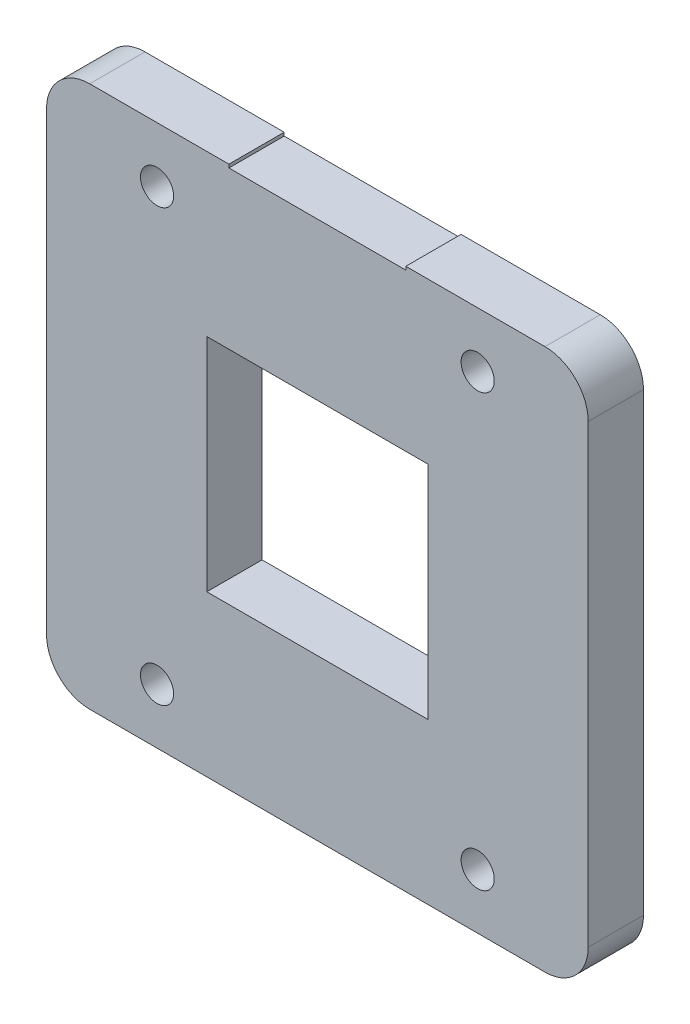
SolidWorks part; units mm, degrees
ref_plane "Front Plane" through (0, 0, 0) normal (0, 0, 1) x (1, 0, 0)
ref_plane "Top Plane" through (0, 0, 0) normal (0, 1, 0) x (1, 0, 0)
ref_plane "Right Plane" through (0, 0, 0) normal (1, 0, 0) x (0, 0, -1)
sketch "Sketch1" plane through (0, 0, 0) normal (0, 0, 1) x (1, 0, 0)
  line L0 (-20.59, 24.5) -> (20.59, 24.5)
  line L1 (-24.5, 20.59) -> (-24.5, -20.59)
  line L2 (-20.59, -24.5) -> (21.2574, -24.5)
  line L3 (24.5, 20.59) -> (24.5, -20.59)
  line L4 (20.59, -24.5) -> (21.2574, -24.5)
  arc A0 (-20.59, 24.5) -> (-24.5, 20.59) centre (-20.59, 20.59) ccw
  arc A1 (-24.5, -20.59) -> (-20.59, -24.5) centre (-20.59, -20.59) ccw
  arc A2 (20.59, 24.5) -> (24.5, 20.59) centre (20.59, 20.59) cw
  arc A3 (24.5, -20.59) -> (20.59, -24.5) centre (20.59, -20.59) cw
  point P2 (0, 24.5)
  point P17 (-24.5, 0)
  dimension "D1" = 3.91
  dimension "D2" = 41.18
  dimension "D3" = 41.18
extrude "Boss-Extrude1" add sketch "Sketch1" along normal blind 5 contours A3 L3 A2 L0 A0 L1 A1 L2 region at (0, 0, 0)
sketch "Sketch2" plane through (0, 0, 5) normal (0, 0, 1) x (1, 0, 0)
  line L6 (-10, -10) -> (10, -10)
  line L7 (-10, -10) -> (-10, 10)
  line L8 (-10, 10) -> (10, 10)
  line L9 (10, -10) -> (10, 10)
  line L10 (-10, -10) -> (10, 10) construction
  line L11 (-10, 10) -> (10, -10) construction
  point P0 (0, 0)
  dimension "D1" = 20
extrude "Cut-Extrude1" cut sketch "Sketch2" against normal blind 5 contours L6 L9 L8 L7 region at (0, 0, 5)
sketch "Sketch5" plane through (0, 0, 5) normal (0, 0, 1) x (1, 0, 0)
  line L2 (-24.5, 20.59) -> (-24.5, -20.59) construction
  line L5 (24.5, 20.59) -> (24.5, -20.59) construction
  line L6 (-20.59, 24.5) -> (20.59, 24.5) construction
  line L7 (-20.59, -24.5) -> (20.59, -24.5) construction
  circle A0 centre (-14.5, 19.5) radius 1.5
  circle A1 centre (14.5, 19.5) radius 1.5
  circle A2 centre (-14.5, -19.5) radius 1.5
  circle A3 centre (14.5, -19.5) radius 1.5
  point P16 (0, 0)
  dimension "D3" = 3
  dimension "D4" = 3
  dimension "D5" = 3
  dimension "D6" = 3
  dimension "D1" = 10
  dimension "D2" = 10
  dimension "D7" = 5
  dimension "D8" = 10
  dimension "D9" = 10
  dimension "D10" = 5
  dimension "D11" = 5
extrude "Cut-Extrude2" cut sketch "Sketch5" against normal through all
sketch "Sketch6" plane through (0, 0, 0) normal (0, 0, -1) x (-1, 0, 0)
  line L0 (21.09, 25) -> (-21.09, 25) construction
  line L1 (-8, 25) -> (8, 25)
  line L2 (-8, 25) -> (-8, 24.2)
  line L3 (-8, 24.2) -> (8, 24.2)
  line L4 (8, 25) -> (8, 24.2)
  point P6 (0, 24.2)
  dimension "D1" = 0.8
  dimension "D2" = 16
extrude "Cut-Extrude3" cut sketch "Sketch6" against normal through all
sketch "Sketch7" plane through (0, 24.5, 0) normal (0, 1, 0) x (1, 0, 0)
  line L0 (-8, -5) -> (-8, 0) construction
  line L2 (8, -5) -> (8, 0) construction
  circle A0 centre (-13, -2.5) radius 1.5
  circle A1 centre (13, -2.5) radius 1.5
  point P5 (-8, -2.5)
  point P9 (8, -2.5)
  dimension "D1" = 3
  dimension "D3" = 3
  dimension "D2" = 5
  dimension "D4" = 5
